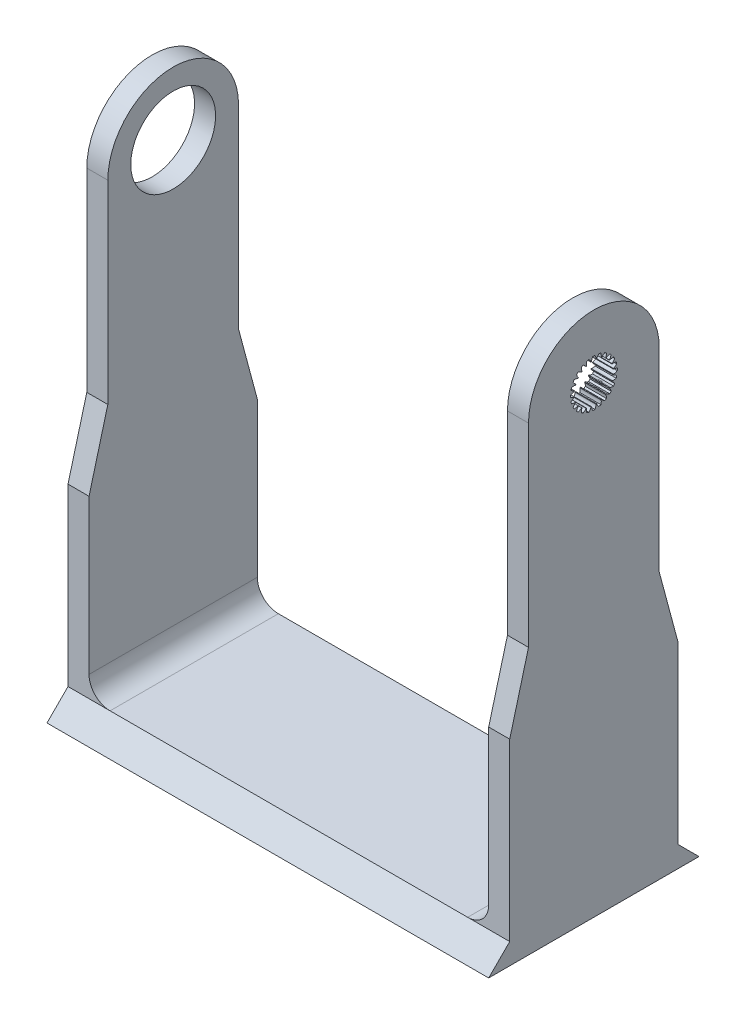
SolidWorks part; units mm, degrees
material "PLA"
ref_plane "Front Plane" through (0, 0, 0) normal (0, 0, 1) x (1, 0, 0)
ref_plane "Top Plane" through (0, 0, 0) normal (0, 1, 0) x (1, 0, 0)
ref_plane "Right Plane" through (0, 0, 0) normal (1, 0, 0) x (0, 0, -1)
sketch "Sketch1" plane through (0, 0, 0) normal (0, 1, 0) x (1, 0, 0)
  line L1 (-31.5, -15) -> (31.5, -15)
  line L2 (-31.5, -15) -> (-31.5, 15)
  line L3 (-31.5, 15) -> (31.5, 15)
  line L4 (31.5, -15) -> (31.5, 15)
  point P4 (0, 15)
  point P6 (31.5, 0)
  dimension "D1" = 63
  dimension "D2" = 30
extrude "Boss-Extrude1" add sketch "Sketch1" along normal blind 3
sketch "Sketch2" plane through (0, 3, 0) normal (0, 1, 0) x (1, 0, 0)
  line L0 (-31.5, 15) -> (-31.5, -15) construction
  line L1 (-31.5, -12) -> (-28.5, -12)
  line L2 (-31.5, -12) -> (-31.5, 12)
  line L3 (-31.5, 12) -> (-28.5, 12)
  line L4 (-28.5, -12) -> (-28.5, 12)
  line L5 (31.5, -15) -> (31.5, 15) construction
  line L6 (31.5, -12) -> (28.5, -12)
  line L7 (31.5, -12) -> (31.5, 12)
  line L8 (31.5, 12) -> (28.5, 12)
  line L9 (28.5, -12) -> (28.5, 12)
  line L10 (31.5, 15) -> (-31.5, 15) construction
  line L11 (-31.5, -15) -> (31.5, -15) construction
  dimension "D1" = 3
  dimension "D2" = 3
  dimension "D3" = 3
  dimension "D4" = 3
  dimension "D5" = 3
  dimension "D6" = 3
extrude "Boss-Extrude2" add sketch "Sketch2" along normal blind 75
sketch "Sketch3" plane through (31.5, 0, 0) normal (1, 0, 0) x (0, 0, -1)
  line L0 (-15, 0) -> (15, 0) construction
  line L1 (-12, 78) -> (12, 78) construction
  line L2 (0, 13) -> (12, 13) construction
  line L3 (12, 78) -> (12, 3) construction
  line L4 (0, 13) -> (0, 66) construction
  line B0 (-2.5678, 64.8835) -> (-2.5895, 64.8732)
  line B1 (-2.2706, 64.3209) -> (-2.2508, 64.3345)
  line B2 (-2.1913, 64.257) -> (-2.2096, 64.2413)
  line B3 (-1.7587, 63.7904) -> (-1.743, 63.8087)
  line B4 (-1.6655, 63.7492) -> (-1.6791, 63.7294)
  line B5 (-1.1268, 63.4105) -> (-1.1165, 63.4322)
  line B6 (-1.0262, 63.3948) -> (-1.0342, 63.3722)
  line B7 (-0.4182, 63.2071) -> (-0.4138, 63.2308)
  line B8 (-0.317, 63.218) -> (-0.3189, 63.194)
  line B9 (0.3189, 63.194) -> (0.317, 63.218)
  line B10 (0.4138, 63.2308) -> (0.4182, 63.2071)
  line B11 (1.0342, 63.3722) -> (1.0262, 63.3948)
  line B12 (1.1165, 63.4322) -> (1.1268, 63.4105)
  line B13 (1.6791, 63.7294) -> (1.6655, 63.7492)
  line B14 (1.743, 63.8087) -> (1.7587, 63.7904)
  line B15 (2.2096, 64.2413) -> (2.1913, 64.257)
  line B16 (2.2508, 64.3345) -> (2.2706, 64.3209)
  line B17 (2.5895, 64.8732) -> (2.5678, 64.8835)
  line B18 (2.6052, 64.9738) -> (2.6278, 64.9658)
  line B19 (2.7929, 65.5818) -> (2.7692, 65.5862)
  line B20 (2.782, 65.683) -> (2.806, 65.6811)
  line B21 (2.806, 66.3189) -> (2.782, 66.317)
  line B22 (2.7692, 66.4138) -> (2.7929, 66.4182)
  line B23 (2.6278, 67.0342) -> (2.6052, 67.0262)
  line B24 (2.5678, 67.1165) -> (2.5895, 67.1268)
  line B25 (2.2706, 67.6791) -> (2.2508, 67.6655)
  line B26 (2.1913, 67.743) -> (2.2096, 67.7587)
  line B27 (1.7587, 68.2096) -> (1.743, 68.1913)
  line B28 (1.6655, 68.2508) -> (1.6791, 68.2706)
  line B29 (1.1268, 68.5895) -> (1.1165, 68.5678)
  line B30 (1.0262, 68.6052) -> (1.0342, 68.6278)
  line B31 (0.4182, 68.7929) -> (0.4138, 68.7692)
  line B32 (0.317, 68.782) -> (0.3189, 68.806)
  line B33 (-0.3189, 68.806) -> (-0.317, 68.782)
  line B34 (-0.4138, 68.7692) -> (-0.4182, 68.7929)
  line B35 (-1.0342, 68.6278) -> (-1.0262, 68.6052)
  line B36 (-1.1165, 68.5678) -> (-1.1268, 68.5895)
  line B37 (-1.6791, 68.2706) -> (-1.6655, 68.2508)
  line B38 (-1.743, 68.1913) -> (-1.7587, 68.2096)
  line B39 (-2.2096, 67.7587) -> (-2.1913, 67.743)
  line B40 (-2.2508, 67.6655) -> (-2.2706, 67.6791)
  line B41 (-2.5895, 67.1268) -> (-2.5678, 67.1165)
  line B42 (-2.6052, 67.0262) -> (-2.6278, 67.0342)
  line B43 (-2.7929, 66.4182) -> (-2.7692, 66.4138)
  line B44 (-2.782, 66.317) -> (-2.806, 66.3189)
  line B45 (-2.806, 65.6811) -> (-2.782, 65.683)
  line B46 (-2.7692, 65.5862) -> (-2.7929, 65.5818)
  line B47 (-2.6278, 64.9658) -> (-2.6052, 64.9738)
  arc B48 (-2.6052, 64.9738) -> (-2.5678, 64.8835) centre (0, 66) ccw
  arc B49 (-2.9635, 64.4594) -> (-2.8159, 64.2038) centre (0, 66) ccw
  arc B50 (-2.2508, 64.3345) -> (-2.1913, 64.257) centre (0, 66) ccw
  arc B51 (-2.4638, 63.7449) -> (-2.2551, 63.5362) centre (0, 66) ccw
  arc B52 (-1.743, 63.8087) -> (-1.6655, 63.7492) centre (0, 66) ccw
  arc B53 (-1.7962, 63.1841) -> (-1.5406, 63.0365) centre (0, 66) ccw
  arc B54 (-1.1165, 63.4322) -> (-1.0262, 63.3948) centre (0, 66) ccw
  arc B55 (-1.0062, 62.8152) -> (-0.7211, 62.7388) centre (0, 66) ccw
  arc B56 (-0.4138, 63.2308) -> (-0.317, 63.218) centre (0, 66) ccw
  arc B57 (-0.1476, 62.6633) -> (0.1476, 62.6633) centre (0, 66) ccw
  arc B58 (0.317, 63.218) -> (0.4138, 63.2308) centre (0, 66) ccw
  arc B59 (0.7211, 62.7388) -> (1.0062, 62.8152) centre (0, 66) ccw
  arc B60 (1.0262, 63.3948) -> (1.1165, 63.4322) centre (0, 66) ccw
  arc B61 (1.5406, 63.0365) -> (1.7962, 63.1841) centre (0, 66) ccw
  arc B62 (1.6655, 63.7492) -> (1.743, 63.8087) centre (0, 66) ccw
  arc B63 (2.2551, 63.5362) -> (2.4638, 63.7449) centre (0, 66) ccw
  arc B64 (2.1913, 64.257) -> (2.2508, 64.3345) centre (0, 66) ccw
  arc B65 (2.8159, 64.2038) -> (2.9635, 64.4594) centre (0, 66) ccw
  arc B66 (2.5678, 64.8835) -> (2.6052, 64.9738) centre (0, 66) ccw
  arc B67 (3.1848, 64.9938) -> (3.2612, 65.2789) centre (0, 66) ccw
  arc B68 (2.7692, 65.5862) -> (2.782, 65.683) centre (0, 66) ccw
  arc B69 (3.3367, 65.8524) -> (3.3367, 66.1476) centre (0, 66) ccw
  arc B70 (2.782, 66.317) -> (2.7692, 66.4138) centre (0, 66) ccw
  arc B71 (3.2612, 66.7211) -> (3.1848, 67.0062) centre (0, 66) ccw
  arc B72 (2.6052, 67.0262) -> (2.5678, 67.1165) centre (0, 66) ccw
  arc B73 (2.9635, 67.5406) -> (2.8159, 67.7962) centre (0, 66) ccw
  arc B74 (2.2508, 67.6655) -> (2.1913, 67.743) centre (0, 66) ccw
  arc B75 (2.4638, 68.2551) -> (2.2551, 68.4638) centre (0, 66) ccw
  arc B76 (1.743, 68.1913) -> (1.6655, 68.2508) centre (0, 66) ccw
  arc B77 (1.7962, 68.8159) -> (1.5406, 68.9635) centre (0, 66) ccw
  arc B78 (1.1165, 68.5678) -> (1.0262, 68.6052) centre (0, 66) ccw
  arc B79 (1.0062, 69.1848) -> (0.7211, 69.2612) centre (0, 66) ccw
  arc B80 (0.4138, 68.7692) -> (0.317, 68.782) centre (0, 66) ccw
  arc B81 (0.1476, 69.3367) -> (-0.1476, 69.3367) centre (0, 66) ccw
  arc B82 (-0.317, 68.782) -> (-0.4138, 68.7692) centre (0, 66) ccw
  arc B83 (-0.7211, 69.2612) -> (-1.0062, 69.1848) centre (0, 66) ccw
  arc B84 (-1.0262, 68.6052) -> (-1.1165, 68.5678) centre (0, 66) ccw
  arc B85 (-1.5406, 68.9635) -> (-1.7962, 68.8159) centre (0, 66) ccw
  arc B86 (-1.6655, 68.2508) -> (-1.743, 68.1913) centre (0, 66) ccw
  arc B87 (-2.2551, 68.4638) -> (-2.4638, 68.2551) centre (0, 66) ccw
  arc B88 (-2.1913, 67.743) -> (-2.2508, 67.6655) centre (0, 66) ccw
  arc B89 (-2.8159, 67.7962) -> (-2.9635, 67.5406) centre (0, 66) ccw
  arc B90 (-2.5678, 67.1165) -> (-2.6052, 67.0262) centre (0, 66) ccw
  arc B91 (-3.1848, 67.0062) -> (-3.2612, 66.7211) centre (0, 66) ccw
  arc B92 (-2.7692, 66.4138) -> (-2.782, 66.317) centre (0, 66) ccw
  arc B93 (-3.3367, 66.1476) -> (-3.3367, 65.8524) centre (0, 66) ccw
  arc B94 (-2.782, 65.683) -> (-2.7692, 65.5862) centre (0, 66) ccw
  arc B95 (-3.2612, 65.2789) -> (-3.1848, 64.9938) centre (0, 66) ccw
  spline B96 degree 3 poles (-2.5895, 64.8732) (-2.6723, 64.8269) (-2.7395, 64.7607) (-2.862, 64.6182) (-2.9137, 64.5392) (-2.9635, 64.4594) knots 0 0 0 0 0.5 0.5 1 1 1 1
  spline B97 degree 3 poles (-2.8159, 64.2038) (-2.722, 64.2071) (-2.628, 64.2123) (-2.4433, 64.2471) (-2.3516, 64.2726) (-2.2706, 64.3209) knots 0 0 0 0 0.5 0.5 1 1 1 1
  spline B98 degree 3 poles (-2.2096, 64.2413) (-2.2776, 64.1752) (-2.3254, 64.0939) (-2.4068, 63.9245) (-2.4363, 63.8349) (-2.4638, 63.7449) knots 0 0 0 0 0.5 0.5 1 1 1 1
  spline B99 degree 3 poles (-2.2551, 63.5362) (-2.1652, 63.5637) (-2.0757, 63.5931) (-1.9063, 63.6744) (-1.8244, 63.7228) (-1.7587, 63.7904) knots 0 0 0 0 0.5 0.5 1 1 1 1
  spline B100 degree 3 poles (-1.6791, 63.7294) (-1.7277, 63.6479) (-1.7529, 63.557) (-1.7877, 63.3723) (-1.7929, 63.2781) (-1.7962, 63.1841) knots 0 0 0 0 0.5 0.5 1 1 1 1
  spline B101 degree 3 poles (-1.5406, 63.0365) (-1.4609, 63.0863) (-1.382, 63.1378) (-1.2395, 63.2603) (-1.1728, 63.3282) (-1.1268, 63.4105) knots 0 0 0 0 0.5 0.5 1 1 1 1
  spline B102 degree 3 poles (-1.0342, 63.3722) (-1.06, 63.2809) (-1.0608, 63.1866) (-1.0466, 62.9992) (-1.0273, 62.9068) (-1.0062, 62.8152) knots 0 0 0 0 0.5 0.5 1 1 1 1
  spline B103 degree 3 poles (-0.7211, 62.7388) (-0.657, 62.8075) (-0.5942, 62.8777) (-0.4881, 63.0328) (-0.4414, 63.1157) (-0.4182, 63.2071) knots 0 0 0 0 0.5 0.5 1 1 1 1
  spline B104 degree 3 poles (-0.3189, 63.194) (-0.3202, 63.0992) (-0.2965, 63.0079) (-0.2343, 62.8305) (-0.1917, 62.7463) (-0.1476, 62.6633) knots 0 0 0 0 0.5 0.5 1 1 1 1
  spline B105 degree 3 poles (0.1476, 62.6633) (0.1917, 62.7462) (0.2342, 62.8303) (0.2965, 63.0076) (0.3202, 63.0998) (0.3189, 63.194) knots 0 0 0 0 0.5 0.5 1 1 1 1
  spline B106 degree 3 poles (0.4182, 63.2071) (0.4415, 63.1152) (0.488, 63.0331) (0.594, 62.8779) (0.6569, 62.8075) (0.7211, 62.7388) knots 0 0 0 0 0.5 0.5 1 1 1 1
  spline B107 degree 3 poles (1.0062, 62.8152) (1.0273, 62.9067) (1.0466, 62.9989) (1.0608, 63.1863) (1.0599, 63.2815) (1.0342, 63.3722) knots 0 0 0 0 0.5 0.5 1 1 1 1
  spline B108 degree 3 poles (1.1268, 63.4105) (1.1731, 63.3277) (1.2393, 63.2605) (1.3818, 63.138) (1.4608, 63.0863) (1.5406, 63.0365) knots 0 0 0 0 0.5 0.5 1 1 1 1
  spline B109 degree 3 poles (1.7962, 63.1841) (1.7929, 63.278) (1.7877, 63.372) (1.7529, 63.5567) (1.7274, 63.6484) (1.6791, 63.7294) knots 0 0 0 0 0.5 0.5 1 1 1 1
  spline B110 degree 3 poles (1.7587, 63.7904) (1.8248, 63.7224) (1.9061, 63.6746) (2.0755, 63.5932) (2.1651, 63.5637) (2.2551, 63.5362) knots 0 0 0 0 0.5 0.5 1 1 1 1
  spline B111 degree 3 poles (2.4638, 63.7449) (2.4363, 63.8348) (2.4069, 63.9243) (2.3256, 64.0937) (2.2772, 64.1756) (2.2096, 64.2413) knots 0 0 0 0 0.5 0.5 1 1 1 1
  spline B112 degree 3 poles (2.2706, 64.3209) (2.3521, 64.2723) (2.443, 64.2471) (2.6277, 64.2123) (2.7219, 64.2071) (2.8159, 64.2038) knots 0 0 0 0 0.5 0.5 1 1 1 1
  spline B113 degree 3 poles (2.9635, 64.4594) (2.9137, 64.5391) (2.8622, 64.618) (2.7397, 64.7605) (2.6718, 64.8272) (2.5895, 64.8732) knots 0 0 0 0 0.5 0.5 1 1 1 1
  spline B114 degree 3 poles (2.6278, 64.9658) (2.7191, 64.94) (2.8134, 64.9392) (3.0008, 64.9534) (3.0932, 64.9727) (3.1848, 64.9938) knots 0 0 0 0 0.5 0.5 1 1 1 1
  spline B115 degree 3 poles (3.2612, 65.2789) (3.1925, 65.343) (3.1223, 65.4058) (2.9672, 65.5119) (2.8843, 65.5586) (2.7929, 65.5818) knots 0 0 0 0 0.5 0.5 1 1 1 1
  spline B116 degree 3 poles (2.806, 65.6811) (2.9008, 65.6798) (2.9921, 65.7035) (3.1695, 65.7657) (3.2537, 65.8083) (3.3367, 65.8524) knots 0 0 0 0 0.5 0.5 1 1 1 1
  spline B117 degree 3 poles (3.3367, 66.1476) (3.2538, 66.1917) (3.1697, 66.2342) (2.9924, 66.2965) (2.9002, 66.3202) (2.806, 66.3189) knots 0 0 0 0 0.5 0.5 1 1 1 1
  spline B118 degree 3 poles (2.7929, 66.4182) (2.8848, 66.4415) (2.9669, 66.488) (3.1221, 66.594) (3.1925, 66.6569) (3.2612, 66.7211) knots 0 0 0 0 0.5 0.5 1 1 1 1
  spline B119 degree 3 poles (3.1848, 67.0062) (3.0933, 67.0273) (3.0011, 67.0466) (2.8137, 67.0608) (2.7185, 67.0599) (2.6278, 67.0342) knots 0 0 0 0 0.5 0.5 1 1 1 1
  spline B120 degree 3 poles (2.5895, 67.1268) (2.6723, 67.1731) (2.7395, 67.2393) (2.862, 67.3818) (2.9137, 67.4608) (2.9635, 67.5406) knots 0 0 0 0 0.5 0.5 1 1 1 1
  spline B121 degree 3 poles (2.8159, 67.7962) (2.722, 67.7929) (2.628, 67.7877) (2.4433, 67.7529) (2.3516, 67.7274) (2.2706, 67.6791) knots 0 0 0 0 0.5 0.5 1 1 1 1
  spline B122 degree 3 poles (2.2096, 67.7587) (2.2776, 67.8248) (2.3254, 67.9061) (2.4068, 68.0755) (2.4363, 68.1651) (2.4638, 68.2551) knots 0 0 0 0 0.5 0.5 1 1 1 1
  spline B123 degree 3 poles (2.2551, 68.4638) (2.1652, 68.4363) (2.0757, 68.4069) (1.9063, 68.3256) (1.8244, 68.2772) (1.7587, 68.2096) knots 0 0 0 0 0.5 0.5 1 1 1 1
  spline B124 degree 3 poles (1.6791, 68.2706) (1.7277, 68.3521) (1.7529, 68.443) (1.7877, 68.6277) (1.7929, 68.7219) (1.7962, 68.8159) knots 0 0 0 0 0.5 0.5 1 1 1 1
  spline B125 degree 3 poles (1.5406, 68.9635) (1.4609, 68.9137) (1.382, 68.8622) (1.2395, 68.7397) (1.1728, 68.6718) (1.1268, 68.5895) knots 0 0 0 0 0.5 0.5 1 1 1 1
  spline B126 degree 3 poles (1.0342, 68.6278) (1.06, 68.7191) (1.0608, 68.8134) (1.0466, 69.0008) (1.0273, 69.0932) (1.0062, 69.1848) knots 0 0 0 0 0.5 0.5 1 1 1 1
  spline B127 degree 3 poles (0.7211, 69.2612) (0.657, 69.1925) (0.5942, 69.1223) (0.4881, 68.9672) (0.4414, 68.8843) (0.4182, 68.7929) knots 0 0 0 0 0.5 0.5 1 1 1 1
  spline B128 degree 3 poles (0.3189, 68.806) (0.3202, 68.9008) (0.2965, 68.9921) (0.2343, 69.1695) (0.1917, 69.2537) (0.1476, 69.3367) knots 0 0 0 0 0.5 0.5 1 1 1 1
  spline B129 degree 3 poles (-0.1476, 69.3367) (-0.1917, 69.2538) (-0.2342, 69.1697) (-0.2965, 68.9924) (-0.3202, 68.9002) (-0.3189, 68.806) knots 0 0 0 0 0.5 0.5 1 1 1 1
  spline B130 degree 3 poles (-0.4182, 68.7929) (-0.4415, 68.8848) (-0.488, 68.9669) (-0.594, 69.1221) (-0.6569, 69.1925) (-0.7211, 69.2612) knots 0 0 0 0 0.5 0.5 1 1 1 1
  spline B131 degree 3 poles (-1.0062, 69.1848) (-1.0273, 69.0933) (-1.0466, 69.0011) (-1.0608, 68.8137) (-1.0599, 68.7185) (-1.0342, 68.6278) knots 0 0 0 0 0.5 0.5 1 1 1 1
  spline B132 degree 3 poles (-1.1268, 68.5895) (-1.1731, 68.6723) (-1.2393, 68.7395) (-1.3818, 68.862) (-1.4608, 68.9137) (-1.5406, 68.9635) knots 0 0 0 0 0.5 0.5 1 1 1 1
  spline B133 degree 3 poles (-1.7962, 68.8159) (-1.7929, 68.722) (-1.7877, 68.628) (-1.7529, 68.4433) (-1.7274, 68.3516) (-1.6791, 68.2706) knots 0 0 0 0 0.5 0.5 1 1 1 1
  spline B134 degree 3 poles (-1.7587, 68.2096) (-1.8248, 68.2776) (-1.9061, 68.3254) (-2.0755, 68.4068) (-2.1651, 68.4363) (-2.2551, 68.4638) knots 0 0 0 0 0.5 0.5 1 1 1 1
  spline B135 degree 3 poles (-2.4638, 68.2551) (-2.4363, 68.1652) (-2.4069, 68.0757) (-2.3256, 67.9063) (-2.2772, 67.8244) (-2.2096, 67.7587) knots 0 0 0 0 0.5 0.5 1 1 1 1
  spline B136 degree 3 poles (-2.2706, 67.6791) (-2.3521, 67.7277) (-2.443, 67.7529) (-2.6277, 67.7877) (-2.7219, 67.7929) (-2.8159, 67.7962) knots 0 0 0 0 0.5 0.5 1 1 1 1
  spline B137 degree 3 poles (-2.9635, 67.5406) (-2.9137, 67.4609) (-2.8622, 67.382) (-2.7397, 67.2395) (-2.6718, 67.1728) (-2.5895, 67.1268) knots 0 0 0 0 0.5 0.5 1 1 1 1
  spline B138 degree 3 poles (-2.6278, 67.0342) (-2.7191, 67.06) (-2.8134, 67.0608) (-3.0008, 67.0466) (-3.0932, 67.0273) (-3.1848, 67.0062) knots 0 0 0 0 0.5 0.5 1 1 1 1
  spline B139 degree 3 poles (-3.2612, 66.7211) (-3.1925, 66.657) (-3.1223, 66.5942) (-2.9672, 66.4881) (-2.8843, 66.4414) (-2.7929, 66.4182) knots 0 0 0 0 0.5 0.5 1 1 1 1
  spline B140 degree 3 poles (-2.806, 66.3189) (-2.9008, 66.3202) (-2.9921, 66.2965) (-3.1695, 66.2343) (-3.2537, 66.1917) (-3.3367, 66.1476) knots 0 0 0 0 0.5 0.5 1 1 1 1
  spline B141 degree 3 poles (-3.3367, 65.8524) (-3.2538, 65.8083) (-3.1697, 65.7658) (-2.9924, 65.7035) (-2.9002, 65.6798) (-2.806, 65.6811) knots 0 0 0 0 0.5 0.5 1 1 1 1
  spline B142 degree 3 poles (-2.7929, 65.5818) (-2.8848, 65.5585) (-2.9669, 65.512) (-3.1221, 65.406) (-3.1925, 65.3431) (-3.2612, 65.2789) knots 0 0 0 0 0.5 0.5 1 1 1 1
  spline B143 degree 3 poles (-3.1848, 64.9938) (-3.0933, 64.9727) (-3.0011, 64.9534) (-2.8137, 64.9392) (-2.7185, 64.9401) (-2.6278, 64.9658) knots 0 0 0 0 0.5 0.5 1 1 1 1
  dimension "D1" = 53
  dimension "D2" = 13
  dimension "D3" = 12
sketch_block_instance "Block2-1"
sketch_block "Block2"
extrude "Cut-Extrude1" cut sketch "Sketch3" against normal up to surface (3 mm away) up to face at (28.5, 40.5, 0)
sketch "Sketch4" plane through (-31.5, 0, 0) normal (-1, 0, 0) x (0, 0, 1)
  circle A0 centre (0, 66) radius 6.05
  dimension "D1" = 12.1
extrude "Cut-Extrude2" cut sketch "Sketch4" against normal up to surface (3 mm away) up to face at (-28.5, 40.5, 0)
sketch "Sketch5" plane through (31.5, 0, 0) normal (1, 0, 0) x (0, 0, -1)
  line L2 (-12, 3) -> (-12, 28)
  line L4 (-12, 78) -> (-12, 3) construction
  line L6 (-12, 28) -> (-9.3205, 38)
  line L11 (-9.3205, 38) -> (-9.3205, 65.7)
  line L12 (12, 3) -> (12, 28)
  line L13 (12, 78) -> (12, 3) construction
  line L14 (12, 28) -> (9.3205, 38)
  line L15 (9.3205, 38) -> (9.3205, 65.7)
  line L16 (-12, 28) -> (-12, 78)
  line L17 (-12, 78) -> (12, 78)
  line L18 (12, 78) -> (12, 28)
  line L19 (12, 78) -> (12, 28)
  arc A3 (-9.3205, 65.7) -> (9.3205, 65.7) centre (0, 65.7) cw
  dimension "D3" = 27.7
  dimension "D4" = 15
  dimension "D1" = 25
  dimension "D2" = 15
  dimension "D6" = 10
  dimension "D7" = 10
  dimension "D8" = 25
  dimension "D9" = 27.7
chamfer "Chamfer1" distance 3 angle 45 2 edges at (0, 3, -15) (0, 3, 15)
fillet "Fillet1" radius 3 2 edges at (-28.5, 3, 0) (28.5, 3, 0)
extrude "Cut-Extrude3" cut sketch "Sketch5" against normal blind 10 contours L11 A3 L15 L14 L18 L17 L16 L6 region at (31.5, 53, 11.4454)
mirror "Mirror1" about plane through (0, 0, 0) normal (1, 0, 0) of "Cut-Extrude3"
